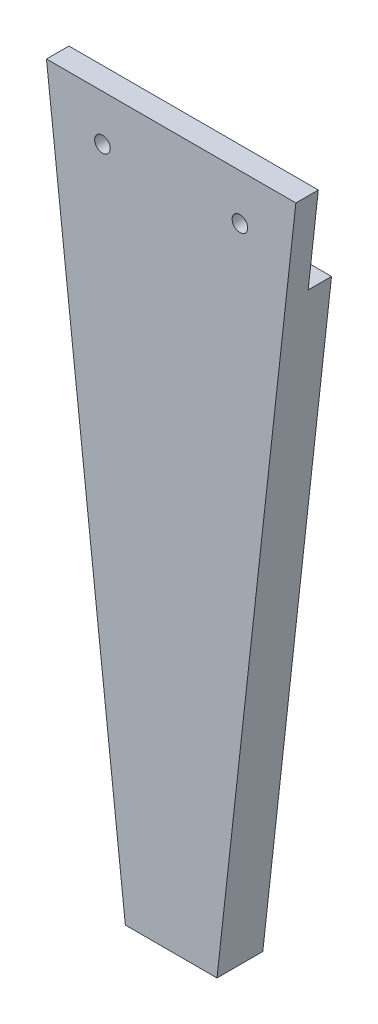
SolidWorks part; units mm, degrees
ref_plane "Front Plane" through (0, 0, 0) normal (0, 0, 1) x (1, 0, 0)
ref_plane "Top Plane" through (0, 0, 0) normal (0, 1, 0) x (1, 0, 0)
ref_plane "Right Plane" through (0, 0, 0) normal (1, 0, 0) x (0, 0, -1)
sketch "Sketch1" plane through (0, 0, 0) normal (0, 0, 1) x (1, 0, 0)
  line L0 (-25, 0) -> (25, 0)
  line L1 (-27.22, 20) -> (27.22, 20)
  line L2 (-27.22, 20) -> (-25, 0)
  line L3 (25, 0) -> (27.22, 20)
  line L4 (0, 20) -> (0, -135.1351) construction
  line L5 (-74.6042, -135.1351) -> (74.6042, -135.1351)
  line L6 (-27.22, 20) -> (-10, -135.1351)
  line L7 (27.22, 20) -> (10, -135.1351)
  point P4 (0, 0)
  point P8 (0, 20)
  point P12 (0, -135.1351)
  dimension "D1" = 50
  dimension "D2" = 54.44
  dimension "D3" = 20
  dimension "D4" = 10
extrude "Boss-Extrude1" add sketch "Sketch1" along normal blind 10 contours L0 L4 L5 L7 | L4 L0 L6 L5 | L1 L4 L0 L3 | L4 L1 L2 L0 region at (-13.0629, 10.1417, 0) region at (-9.2857, -57.9151, 0) region at (13.0629, 10.1417, 0) region at (9.2857, -57.9151, 0)
extrude "Cut-Extrude1" cut sketch "Sketch1<3>" along normal blind 5.1 contours L1 L4 L0 L3 | L4 L1 L2 L0 region at (-13.0629, 10.1417, 0) region at (13.0629, 10.1417, 0)
sketch "Sketch1<3>" plane through (0, 0, 0) normal (0, 0, 1) x (1, 0, 0) same geometry as "Sketch1"
sketch "Sketch2" plane through (0, 0, 5.1) normal (0, 0, -1) x (-1, 0, 0)
  line L0 (0, 20) -> (0, 10) construction
  line L1 (27.22, 20) -> (-27.22, 20) construction
  line L2 (-15, 10) -> (15, 10) construction
  circle A0 centre (-15, 10) radius 1.7
  circle A1 centre (15, 10) radius 1.7
  point P8 (0, 10)
extrude "Cut-Extrude2" cut sketch "Sketch2" against normal blind 5.1
